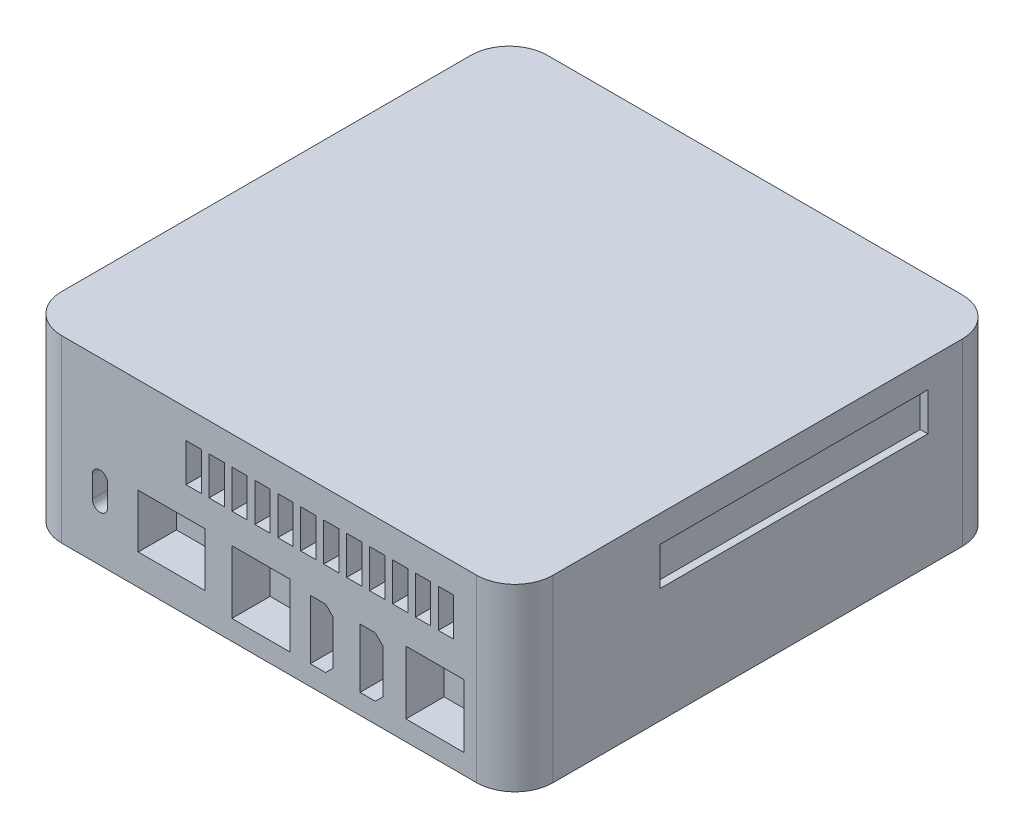
SolidWorks part; units mm, degrees
ref_plane "Front Plane" through (0, 0, 0) normal (0, 0, 1) x (1, 0, 0)
ref_plane "Top Plane" through (0, 0, 0) normal (0, 1, 0) x (1, 0, 0)
ref_plane "Right Plane" through (0, 0, 0) normal (1, 0, 0) x (0, 0, -1)
sketch "Sketch1" plane through (0, 0, 0) normal (0, 1, 0) x (1, 0, 0)
  line L1 (0, 0) -> (128.5, 0)
  line L2 (0, 0) -> (0, 127)
  line L3 (0, 127) -> (128.5, 127)
  line L4 (128.5, 0) -> (128.5, 127)
  dimension "D1" = 127
  dimension "D2" = 128.5
extrude "gabaryt" add sketch "Sketch1" along normal blind 47
sketch "Sketch2" plane through (0, 0, 0) normal (0, 0, 1) x (1, 0, 0)
  line L0 (20, 19.6) -> (20, 14) construction
  line L1 (22, 19.6) -> (22, 14)
  line L2 (18, 19.6) -> (18, 14)
  line L3 (0, 47) -> (0, 0) construction
  line L4 (75, 20.7) -> (75, 5.2)
  line L5 (30, 22) -> (47.5, 22)
  line L6 (30, 22) -> (30, 8)
  line L7 (30, 8) -> (47.5, 8)
  line L8 (47.5, 22) -> (47.5, 8)
  line L9 (54.5, 21.7) -> (69.7, 21.7)
  line L10 (54.5, 21.7) -> (54.5, 5.2)
  line L11 (54.5, 5.2) -> (69.7, 5.2)
  line L12 (69.7, 21.7) -> (69.7, 5.2)
  line L14 (81, 7.2) -> (81, 18.7)
  line L16 (88, 20.7) -> (88, 5.2)
  line L18 (94, 7.2) -> (94, 18.7)
  line L20 (81, 18.7) -> (79, 20.7)
  line L21 (100, 21.7) -> (115.2, 21.7)
  line L22 (100, 21.7) -> (100, 5.2)
  line L23 (100, 5.2) -> (115.2, 5.2)
  line L24 (115.2, 21.7) -> (115.2, 5.2)
  line L25 (79, 20.7) -> (75, 20.7)
  line L26 (81, 7.2) -> (79, 5.2)
  line L27 (79, 5.2) -> (75, 5.2)
  line L28 (94, 18.7) -> (92, 20.7)
  line L29 (92, 20.7) -> (88, 20.7)
  line L30 (94, 7.2) -> (92, 5.2)
  line L31 (92, 5.2) -> (88, 5.2)
  line L32 (0, 0) -> (128.5, 0) construction
  arc A0 (22, 19.6) -> (18, 19.6) centre (20, 19.6) ccw
  arc A1 (18, 14) -> (22, 14) centre (20, 14) ccw
  point P2 (20, 16.8)
  point P23 (18, 16.8)
  point P27 (20, 12)
  point P31 (20, 21.6)
  point P32 (91.5393, 26.992)
  point P37 (92, 14.3072)
  dimension "D1" = 18
  dimension "D2" = 30
  dimension "D3" = 54.5
  dimension "D4" = 75
  dimension "D5" = 88
  dimension "D6" = 100
  dimension "D7" = 4
  dimension "D8" = 9.6
  dimension "D9" = 17.5
  dimension "D10" = 14
  dimension "D11" = 15.2
  dimension "D12" = 16.5
  dimension "D13" = 6
  dimension "D14" = 6
  dimension "D15" = 15.5
  dimension "D16" = 4
  dimension "D17" = 45
  dimension "D18" = 45
  dimension "D19" = 45
  dimension "D20" = 45
  dimension "D21" = 5.2
  dimension "D22" = 8
  dimension "D23" = 12
extrude "porty (usbc/ethernet/2xUSBa/hdmi/hdmi/2xUSBa)" cut sketch "Sketch2" against normal blind 10
sketch "Sketch3" plane through (0, 0, 0) normal (0, 0, 1) x (1, 0, 0)
  line L1 (42.5, 39.5) -> (112.5, 39.5)
  line L2 (42.5, 39.5) -> (42.5, 29.5)
  line L3 (42.5, 29.5) -> (112.5, 29.5)
  line L4 (112.5, 39.5) -> (112.5, 29.5)
  line L5 (0, 0) -> (128.5, 0) construction
  line L6 (128.5, 47) -> (128.5, 0) construction
  line L7 (100.5, 39.5) -> (100.5, 29.5)
  line L8 (108.5, 39.5) -> (106.5, 39.5)
  line L9 (108.5, 39.5) -> (108.5, 29.5)
  line L10 (108.5, 29.5) -> (106.5, 29.5)
  line L11 (106.5, 39.5) -> (106.5, 29.5)
  line L12 (102.5, 39.5) -> (102.5, 29.5)
  line L13 (102.5, 39.5) -> (100.5, 39.5)
  line L14 (102.5, 29.5) -> (100.5, 29.5)
  line L15 (94.5, 39.5) -> (94.5, 29.5)
  line L16 (96.5, 39.5) -> (96.5, 29.5)
  line L17 (96.5, 39.5) -> (94.5, 39.5)
  line L18 (96.5, 29.5) -> (94.5, 29.5)
  line L19 (88.5, 39.5) -> (88.5, 29.5)
  line L20 (90.5, 39.5) -> (90.5, 29.5)
  line L21 (90.5, 39.5) -> (88.5, 39.5)
  line L22 (90.5, 29.5) -> (88.5, 29.5)
  line L23 (82.5, 39.5) -> (82.5, 29.5)
  line L24 (84.5, 39.5) -> (84.5, 29.5)
  line L25 (84.5, 39.5) -> (82.5, 39.5)
  line L26 (84.5, 29.5) -> (82.5, 29.5)
  line L27 (76.5, 39.5) -> (76.5, 29.5)
  line L28 (78.5, 39.5) -> (78.5, 29.5)
  line L29 (78.5, 39.5) -> (76.5, 39.5)
  line L30 (78.5, 29.5) -> (76.5, 29.5)
  line L31 (70.5, 39.5) -> (70.5, 29.5)
  line L32 (72.5, 39.5) -> (72.5, 29.5)
  line L33 (72.5, 39.5) -> (70.5, 39.5)
  line L34 (72.5, 29.5) -> (70.5, 29.5)
  line L35 (64.5, 39.5) -> (64.5, 29.5)
  line L36 (66.5, 39.5) -> (66.5, 29.5)
  line L37 (66.5, 39.5) -> (64.5, 39.5)
  line L38 (66.5, 29.5) -> (64.5, 29.5)
  line L39 (58.5, 39.5) -> (58.5, 29.5)
  line L40 (60.5, 39.5) -> (60.5, 29.5)
  line L41 (60.5, 39.5) -> (58.5, 39.5)
  line L42 (60.5, 29.5) -> (58.5, 29.5)
  line L43 (52.5, 39.5) -> (52.5, 29.5)
  line L44 (54.5, 39.5) -> (54.5, 29.5)
  line L45 (54.5, 39.5) -> (52.5, 39.5)
  line L46 (54.5, 29.5) -> (52.5, 29.5)
  line L47 (46.5, 39.5) -> (46.5, 29.5)
  line L48 (48.5, 39.5) -> (48.5, 29.5)
  line L49 (48.5, 39.5) -> (46.5, 39.5)
  line L50 (48.5, 29.5) -> (46.5, 29.5)
  dimension "D1" = 70
  dimension "D2" = 10
  dimension "D3" = 29.5
  dimension "D4" = 16
  dimension "D5" = 2
  dimension "D6" = 4
  dimension "D7" = 11
extrude "vents outlet 1" cut sketch "Sketch3" against normal blind 10 contours L47 L1 L2 L3 | L1 L48 L3 L43 | L1 L44 L3 L39 | L1 L40 L3 L35 | L1 L36 L3 L31 | L1 L32 L3 L27 | L1 L28 L3 L23 | L1 L24 L3 L19 | L1 L20 L3 L15 | L1 L16 L3 L7 | L1 L12 L3 L11 | L1 L9 L3 L4 region at (44.5, 34.5, 0) region at (50.5, 34.5, 0) region at (56.5, 34.5, 0) region at (62.5, 34.5, 0) region at (68.5, 34.5, 0) region at (74.5, 34.5, 0) region at (80.5, 34.5, 0) region at (86.5, 34.5, 0) region at (92.5, 34.5, 0) region at (98.5, 34.5, 0) region at (104.5, 34.5, 0) region at (110.5, 34.5, 0)
sketch "Sketch4" plane through (0, 0, 0) normal (-1, 0, 0) x (0, 0, 1)
  line L0 (-127, 47) -> (-127, 0) construction
  line L1 (-108, 40) -> (-38, 40)
  line L2 (-108, 40) -> (-108, 30)
  line L3 (-108, 30) -> (-38, 30)
  line L4 (-38, 40) -> (-38, 30)
  line L5 (-127, 0) -> (0, 0) construction
  line L6 (-98, 40) -> (-98, 30)
  line L7 (-104, 40) -> (-102, 40)
  line L8 (-104, 40) -> (-104, 30)
  line L9 (-104, 30) -> (-102, 30)
  line L10 (-102, 40) -> (-102, 30)
  line L11 (-98, 40) -> (-96, 40)
  line L12 (-96, 40) -> (-96, 30)
  line L13 (-98, 30) -> (-96, 30)
  line L14 (-92, 40) -> (-92, 30)
  line L15 (-92, 40) -> (-90, 40)
  line L16 (-90, 40) -> (-90, 30)
  line L17 (-92, 30) -> (-90, 30)
  line L18 (-86, 40) -> (-86, 30)
  line L19 (-86, 40) -> (-84, 40)
  line L20 (-84, 40) -> (-84, 30)
  line L21 (-86, 30) -> (-84, 30)
  line L22 (-80, 40) -> (-80, 30)
  line L23 (-80, 40) -> (-78, 40)
  line L24 (-78, 40) -> (-78, 30)
  line L25 (-80, 30) -> (-78, 30)
  line L26 (-74, 40) -> (-74, 30)
  line L27 (-74, 40) -> (-72, 40)
  line L28 (-72, 40) -> (-72, 30)
  line L29 (-74, 30) -> (-72, 30)
  line L30 (-68, 40) -> (-68, 30)
  line L31 (-68, 40) -> (-66, 40)
  line L32 (-66, 40) -> (-66, 30)
  line L33 (-68, 30) -> (-66, 30)
  line L34 (-62, 40) -> (-62, 30)
  line L35 (-62, 40) -> (-60, 40)
  line L36 (-60, 40) -> (-60, 30)
  line L37 (-62, 30) -> (-60, 30)
  line L38 (-56, 40) -> (-56, 30)
  line L39 (-56, 40) -> (-54, 40)
  line L40 (-54, 40) -> (-54, 30)
  line L41 (-56, 30) -> (-54, 30)
  line L42 (-50, 40) -> (-50, 30)
  line L43 (-50, 40) -> (-48, 40)
  line L44 (-48, 40) -> (-48, 30)
  line L45 (-50, 30) -> (-48, 30)
  line L46 (-44, 40) -> (-44, 30)
  line L47 (-44, 40) -> (-42, 40)
  line L48 (-42, 40) -> (-42, 30)
  line L49 (-44, 30) -> (-42, 30)
  dimension "D1" = 19
  dimension "D2" = 30
  dimension "D3" = 10
  dimension "D4" = 70
  dimension "D5" = 2
  dimension "D6" = 4
  dimension "D7" = 11
extrude "vents outlet 2" cut sketch "Sketch4" against normal blind 10 contours L8 L1 L2 L3 | L1 L10 L3 L6 | L14 L1 L12 L3 | L18 L1 L16 L3 | L22 L1 L20 L3 | L26 L1 L24 L3 | L30 L1 L28 L3 | L34 L1 L32 L3 | L38 L1 L36 L3 | L42 L1 L40 L3 | L46 L1 L44 L3 | L1 L48 L3 L4 region at (0, 35, -106) region at (0, 35, -100) region at (0, 35, -94) region at (0, 35, -88) region at (0, 35, -82) region at (0, 35, -76) region at (0, 35, -70) region at (0, 35, -64) region at (0, 35, -58) region at (0, 35, -52) region at (0, 35, -46) region at (0, 35, -40)
extrude "vents inlet 1" cut sketch "Sketch3<3>" along normal blind 2 from surface contours L47 L1 L2 L3 | L48 L1 L47 L3 | L1 L48 L3 L43 | L44 L1 L43 L3 | L1 L40 L3 L35 | L1 L44 L3 L39 | L36 L1 L35 L3 | L40 L1 L39 L3 | L1 L36 L3 L31 | L32 L1 L31 L3 | L1 L32 L3 L27 | L28 L1 L27 L3 | L1 L28 L3 L23 | L24 L1 L23 L3 | L1 L24 L3 L19 | L20 L1 L19 L3 | L1 L20 L3 L15 | L16 L1 L15 L3 | L1 L16 L3 L7 | L12 L1 L7 L3 | L1 L12 L3 L11 | L1 L9 L3 L4 | L1 L11 L3 L9 | L39 L42 L40 L41 region at (44.5, 34.5, 0) region at (47.5, 34.5, 0) region at (50.5, 34.5, 0) region at (53.5, 34.5, 0) region at (56.5, 34.5, 0) region at (59.5, 34.5, 0) region at (62.5, 34.5, 0) region at (65.5, 34.5, 0) region at (68.5, 34.5, 0) region at (71.5, 34.5, 0) region at (74.5, 34.5, 0) region at (77.5, 34.5, 0) region at (80.5, 34.5, 0) region at (83.5, 34.5, 0) region at (86.5, 34.5, 0) region at (89.5, 34.5, 0) region at (92.5, 34.5, 0) region at (95.5, 34.5, 0) region at (98.5, 34.5, 0) region at (101.5, 34.5, 0) region at (104.5, 34.5, 0) region at (107.5, 34.5, 0) region at (110.5, 34.5, 0) starting at face at (64.25, 23.5, -127)
sketch "Sketch3<3>" plane through (0, 0, 0) normal (0, 0, 1) x (1, 0, 0) same geometry as "Sketch3"
extrude "vents inlet 2" cut sketch "Sketch4<3>" along normal blind 2 from surface contours L1 L4 L3 L2 starting at face at (128.5, 23.5, -63.5)
sketch "Sketch4<3>" plane through (0, 0, 0) normal (-1, 0, 0) x (0, 0, 1) same geometry as "Sketch4"
sketch "Sketch5" plane through (0, 0, -127) normal (0, 0, -1) x (-1, 0, 0)
  line L0 (-128.5, 47) -> (-128.5, 0) construction
  line L1 (-95.5, 20) -> (-85.5, 20)
  line L2 (-95.5, 20) -> (-95.5, 14.5)
  line L3 (-95.5, 14.5) -> (-85.5, 14.5)
  line L4 (-85.5, 20) -> (-85.5, 14.5)
  line L5 (-128.5, 0) -> (0, 0) construction
  line L6 (-60.5, 17.25) -> (-54.5, 17.25) construction
  line L7 (-60.5, 19.25) -> (-54.5, 19.25)
  line L8 (-60.5, 15.25) -> (-54.5, 15.25)
  line L9 (-41, 17.25) -> (-35, 17.25) construction
  line L10 (-41, 19.25) -> (-35, 19.25)
  line L11 (-41, 15.25) -> (-35, 15.25)
  circle A0 centre (-74.25, 17.25) radius 3.25
  arc A1 (-60.5, 19.25) -> (-60.5, 15.25) centre (-60.5, 17.25) ccw
  arc A2 (-54.5, 15.25) -> (-54.5, 19.25) centre (-54.5, 17.25) ccw
  arc A3 (-41, 19.25) -> (-41, 15.25) centre (-41, 17.25) ccw
  arc A4 (-35, 15.25) -> (-35, 19.25) centre (-35, 17.25) ccw
  point P12 (-57.5, 17.25)
  point P17 (-38, 17.25)
  point P24 (-62.5, 17.25)
  point P25 (-43, 17.25)
  point P26 (-48.1604, 17.25)
  point P27 (-52.5, 17.25)
  dimension "D5" = 6.5
  dimension "D1" = 43
  dimension "D2" = 10
  dimension "D3" = 5.5
  dimension "D4" = 20
  dimension "D6" = 17.25
  dimension "D7" = 21.25
  dimension "D8" = 33
  dimension "D9" = 52.5
  dimension "D10" = 4
  dimension "D11" = 10
extrude "porty (on/audiojack/USBc/USBc)" cut sketch "Sketch5" against normal blind 10
hole_wizard "Tap Drill for M4 Tap1" positions "Sketch6" profile "Sketch8" hole size "M4" standard "DIN"
sketch "Sketch6" plane through (0, 0, 0) normal (0, -1, 0) x (-1, 0, 0)
  line L0 (-64.25, 127) -> (-64.25, 106)
  line L1 (-128.5, 127) -> (0, 127) construction
  line L2 (-64.25, 106) -> (-64.25, 21)
  line L4 (0, 0) -> (-128.5, 0) construction
  point P0 (-64.25, 106)
  point P2 (-64.25, 21)
  point P13 (0, 0)
  dimension "D1" = 21
  dimension "D2" = 21
sketch "Sketch8" plane through (64.25, 0, -106) normal (1, 0, 0) x (0, 0, -1)
  line L0 (0, 0) -> (0, 6.9914)
  line L1 (0, 6.9914) -> (1.65, 6)
  line L2 (1.65, 6) -> (1.65, 0)
  line L5 (1.65, 0) -> (0, 0)
  line L10 (0, 6.9914) -> (-1.65, 6) construction
  line L11 (0, -6.35) -> (0, 107.95) construction
  dimension "Hole Dia." = 3.3
  dimension "Hole Depth" = 6
  dimension "Drill Angle" = 118
fillet "Fillet1" radius 10 4 edges at (0, 23.5, -127) (0, 23.5, 0) (128.5, 23.5, -127) (128.5, 23.5, 0)
